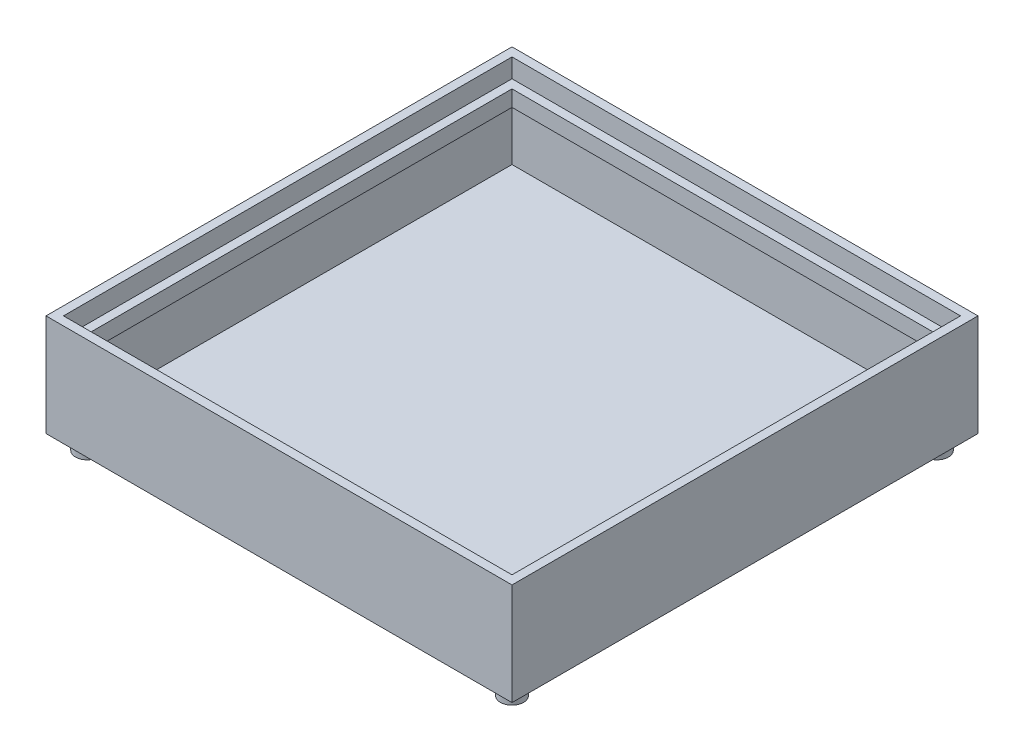
SolidWorks part; units mm, degrees
ref_plane "Front Plane" through (0, 0, 0) normal (0, 0, 1) x (1, 0, 0)
ref_plane "Top Plane" through (0, 0, 0) normal (0, 1, 0) x (1, 0, 0)
ref_plane "Right Plane" through (0, 0, 0) normal (1, 0, 0) x (0, 0, -1)
sketch "Sketch2" plane through (0, 0, 0) normal (0, 1, 0) x (1, 0, 0)
  line L1 (-80, -80) -> (80, -80)
  line L2 (-80, -80) -> (-80, 80)
  line L3 (-80, 80) -> (80, 80)
  line L4 (80, -80) -> (80, 80)
  line L5 (-80, -80) -> (80, 80) construction
  line L6 (-80, 80) -> (80, -80) construction
  point P0 (0, 0)
  dimension "D1" = 160
  dimension "D2" = 160
extrude "Outer Block" add sketch "Sketch2" along normal blind 35
sketch "Sketch12" plane through (0, 35, 0) normal (0, 1, 0) x (1, 0, 0)
  line L1 (77, -77) -> (-77, -77)
  line L2 (77, -77) -> (77, 77)
  line L3 (77, 77) -> (-77, 77)
  line L4 (-77, -77) -> (-77, 77)
  line L5 (77, -77) -> (-77, 77) construction
  line L6 (77, 77) -> (-77, -77) construction
  point P0 (0, 0)
  dimension "D1" = 154
  dimension "D2" = 154
extrude "Cut-Extrude1" cut sketch "Sketch12" against normal blind 6.5
ref_plane "Plane2" through (0, 3, 0) normal (0, -1, 0) x (-1, 0, 0)
sketch "Sketch14" plane through (0, 3, 0) normal (0, -1, 0) x (-1, 0, 0)
  line L1 (-77, -77) -> (77, -77)
  line L2 (-77, -77) -> (-77, 77)
  line L3 (-77, 77) -> (77, 77)
  line L4 (77, -77) -> (77, 77)
  line L5 (-77, -77) -> (77, 77) construction
  line L6 (-77, 77) -> (77, -77) construction
  point P0 (0, 0)
  dimension "D1" = 154
  dimension "D2" = 154
extrude "Cut-Extrude4" cut sketch "Sketch14" against normal blind 20
sketch "Sketch15" plane through (0, 28.5, 0) normal (0, 1, 0) x (1, 0, 0)
  line L1 (-74, -74) -> (74, -74)
  line L2 (-74, -74) -> (-74, 74)
  line L3 (-74, 74) -> (74, 74)
  line L4 (74, -74) -> (74, 74)
  line L5 (-74, -74) -> (74, 74) construction
  line L6 (-74, 74) -> (74, -74) construction
  point P0 (0, 0)
  dimension "D1" = 148
  dimension "D2" = 148
extrude "Cut-Extrude6" cut sketch "Sketch15" against normal blind 7.5
sketch "Sketch17" plane through (0, 0, 0) normal (0, -1, 0) x (1, 0, 0)
  line L0 (-80, 80) -> (-72.9289, 72.9289) construction
  circle A0 centre (-72.9289, 72.9289) radius 4
  dimension "D2" = 8
  dimension "D1" = 10
extrude "Boss-Extrude1" add sketch "Sketch17" along normal blind 5 contours A0
mirror "Mirror1" about plane through (0, 0, 0) normal (0, 0, 1) of "Boss-Extrude1" second plane through (0, 0, 0) second plane normal (1, 0, 0)
